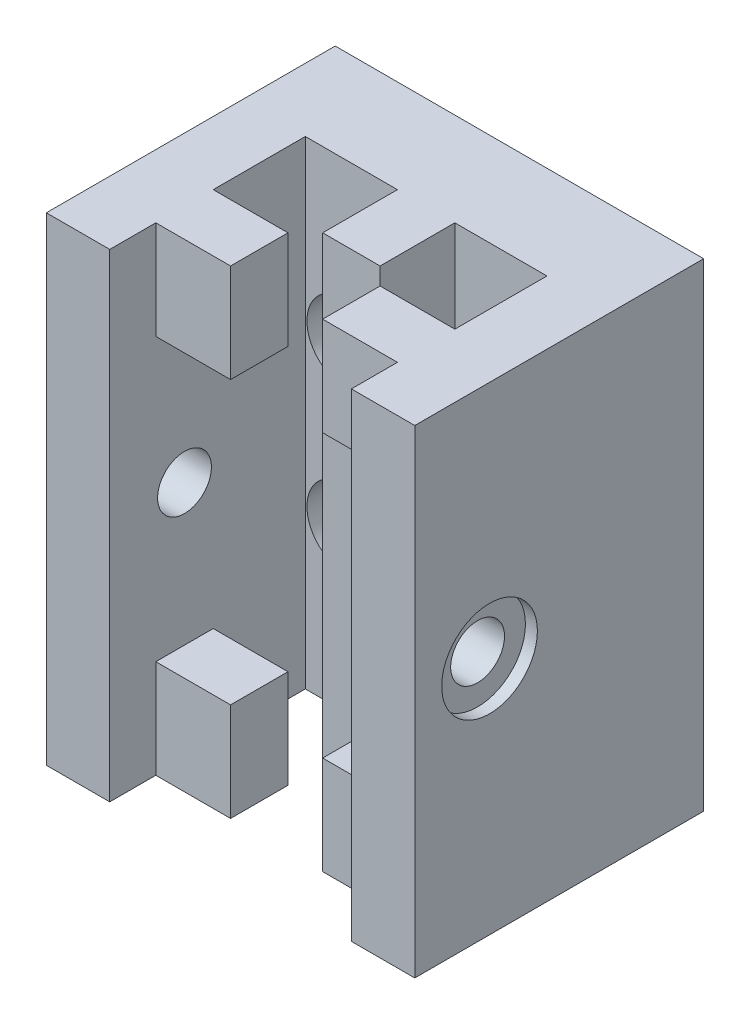
SolidWorks part; units mm, degrees
ref_plane "Plan de face" through (0, 0, 0) normal (0, 0, 1) x (1, 0, 0)
ref_plane "Plan de dessus" through (0, 0, 0) normal (0, 1, 0) x (1, 0, 0)
ref_plane "Plan de droite" through (0, 0, 0) normal (1, 0, 0) x (0, 0, -1)
sketch "Base" plane through (0, 0, 0) normal (0, 1, 0) x (1, 0, 0)
  line L0 (-3.85, -2.4) -> (-3.85, 2.4)
  line L1 (-3.85, 2.4) -> (-10.1, 2.4)
  line L2 (-10.1, 2.4) -> (-10.1, 10.1)
  line L3 (-10.1, 10.1) -> (-2.4, 10.1)
  line L4 (-2.4, 10.1) -> (-2.4, 3.85)
  line L5 (-2.4, 3.85) -> (2.4, 3.85)
  line L6 (0, -55) -> (0, 55) construction
  line L7 (2.4, 10.1) -> (2.4, 3.85)
  line L8 (10.1, 10.1) -> (2.4, 10.1)
  line L9 (10.1, 2.4) -> (10.1, 10.1)
  line L10 (3.85, 2.4) -> (10.1, 2.4)
  line L11 (3.85, -2.4) -> (3.85, 2.4)
  line L12 (-55, 0) -> (55, 0) construction
  line L13 (3.85, -2.4) -> (10.1, -2.4)
  line L14 (10.1, -2.4) -> (10.1, -6.25)
  line L20 (-10.1, -2.4) -> (-10.1, -6.25)
  line L21 (-3.85, -2.4) -> (-10.1, -2.4)
  line L23 (-15.4, 15.4) -> (15.4, 15.4)
  line L24 (-15.4, 15.4) -> (-15.4, -6.25)
  line L26 (15.4, 15.4) -> (15.4, -6.25)
  line L27 (-15.4, 15.4) -> (0, 0) construction
  line L28 (0, 0) -> (15.4, 15.4) construction
  line L29 (-10.1, -6.25) -> (-15.4, -6.25)
  line L30 (10.1, -6.25) -> (15.4, -6.25)
  line L31 (10.1, -10.1) -> (15.4, -15.4) construction
  point P2 (-3.85, 0)
  point P3 (0, 3.85)
  point P24 (0, 0)
  point P27 (0, 0)
  dimension "D1" = 4.8
  dimension "D2" = 4.8
  dimension "D3" = 6.25
  dimension "D4" = 7.7
  dimension "D5" = 30.8
extrude "Boss.-Extru.1" add sketch "Base" along normal mid plane 40
hole_wizard "Chambrage pour vis à six pans creux M41" positions "Esquisse4" profile "Esquisse5" counterbore size "M4" standard "ISO" end condition up to next
sketch "Esquisse4" plane through (15.4, 0, 0) normal (1, 0, 0) x (0, 0, -1)
  point P0 (0, 0)
sketch "Esquisse5" plane through (15.4, 0, 0) normal (0, 1, 0) x (0, 0, -1)
  line L0 (0, 0) -> (0, 11.55)
  line L1 (0, 11.55) -> (2.25, 11.55)
  line L3 (2.25, 11.55) -> (2.25, 1)
  line L4 (2.25, 1) -> (4, 1)
  line L5 (4, 1) -> (4, 0)
  line L7 (4, 0) -> (0, 0)
  line L11 (0, -6.35) -> (0, 107.95) construction
  dimension "Diamètre du perçage jusqu'au prochain" = 4.5
  dimension "Profondeur du perçage jusqu'au prochain" = 11.55
  dimension "Diamètre du chambrage" = 8
  dimension "Profondeur du chambrage" = 1
mirror "Symétrie1" about plane through (0, 0, 0) normal (1, 0, 0) of "Chambrage pour vis à six pans creux M41"
sketch "Esquisse6" plane through (0, 0, 0) normal (0, 0, 1) x (1, 0, 0)
  line L0 (10.1, 20) -> (10.1, -20) construction
  line L1 (-10.1, 11.7753) -> (10.1, 11.7753)
  line L2 (-10.1, 11.7753) -> (-10.1, -11.7753)
  line L3 (-10.1, -11.7753) -> (10.1, -11.7753)
  line L4 (10.1, 11.7753) -> (10.1, -11.7753)
  line L5 (-10.1, 11.7753) -> (10.1, -11.7753) construction
  line L6 (-10.1, -11.7753) -> (10.1, 11.7753) construction
  point P0 (0, 0)
extrude "Enlèv. mat.-Extru.1" cut sketch "Esquisse6" against normal mid plane 6
sketch "Esquisse7" plane through (0, 0, -10.1) normal (0, 0, 1) x (1, 0, 0)
  line L1 (-6.7175, 6.7175) -> (6.7175, 6.7175) construction
  line L2 (-6.7175, 6.7175) -> (-6.7175, -6.7175) construction
  line L3 (-6.7175, -6.7175) -> (6.7175, -6.7175) construction
  line L4 (6.7175, 6.7175) -> (6.7175, -6.7175) construction
  line L5 (-6.7175, 6.7175) -> (6.7175, -6.7175) construction
  line L6 (-6.7175, -6.7175) -> (6.7175, 6.7175) construction
  circle A0 centre (0, 0) radius 9.5 construction
  dimension "D1" = 19
sketch "Esquisse14" plane through (0, -20, 0) normal (0, -1, 0) x (1, 0, 0)
  line L0 (15.4, 6.25) -> (15.4, -15.4) construction
  line L1 (-15.4, -15.4) -> (15.4, -15.4)
  line L2 (-15.4, -15.4) -> (-15.4, -17.9)
  line L3 (-15.4, -17.9) -> (15.4, -17.9)
  line L4 (15.4, -15.4) -> (15.4, -17.9)
  point P4 (14.5485, -17.9)
  dimension "D1" = 2.5
extrude "Boss.-Extru.3" add sketch "Esquisse14" against normal up to vertex (40 mm away) up to point (-15.4, 20, -15.4)
hole_wizard "Chambrage pour vis à six pans creux M31" positions "Esquisse10" profile "Esquisse12" counterbore size "M3" standard "ISO" end condition up to next
sketch "Esquisse10" plane through (0, 0, -10.1) normal (0, 0, 1) x (1, 0, 0)
  point P0 (-6.7175, 6.7175)
  point P3 (-6.7175, -6.7175)
  point P7 (6.7175, 6.7175)
  point P10 (6.7175, -6.7175)
sketch "Esquisse12" plane through (-6.7175, 6.7175, -10.1) normal (1, 0, 0) x (0, -1, 0)
  line L0 (0, 0) -> (0, 7.8)
  line L1 (0, 7.8) -> (1.7, 7.8)
  line L3 (1.7, 7.8) -> (1.7, 3.4)
  line L4 (1.7, 3.4) -> (3.25, 3.4)
  line L5 (3.25, 3.4) -> (3.25, 0)
  line L7 (3.25, 0) -> (0, 0)
  line L11 (0, -6.35) -> (0, 107.95) construction
  dimension "Diamètre du perçage jusqu'au prochain" = 3.4
  dimension "Profondeur du perçage jusqu'au prochain" = 7.8
  dimension "Diamètre du chambrage" = 6.5
  dimension "Profondeur du chambrage" = 3.4
